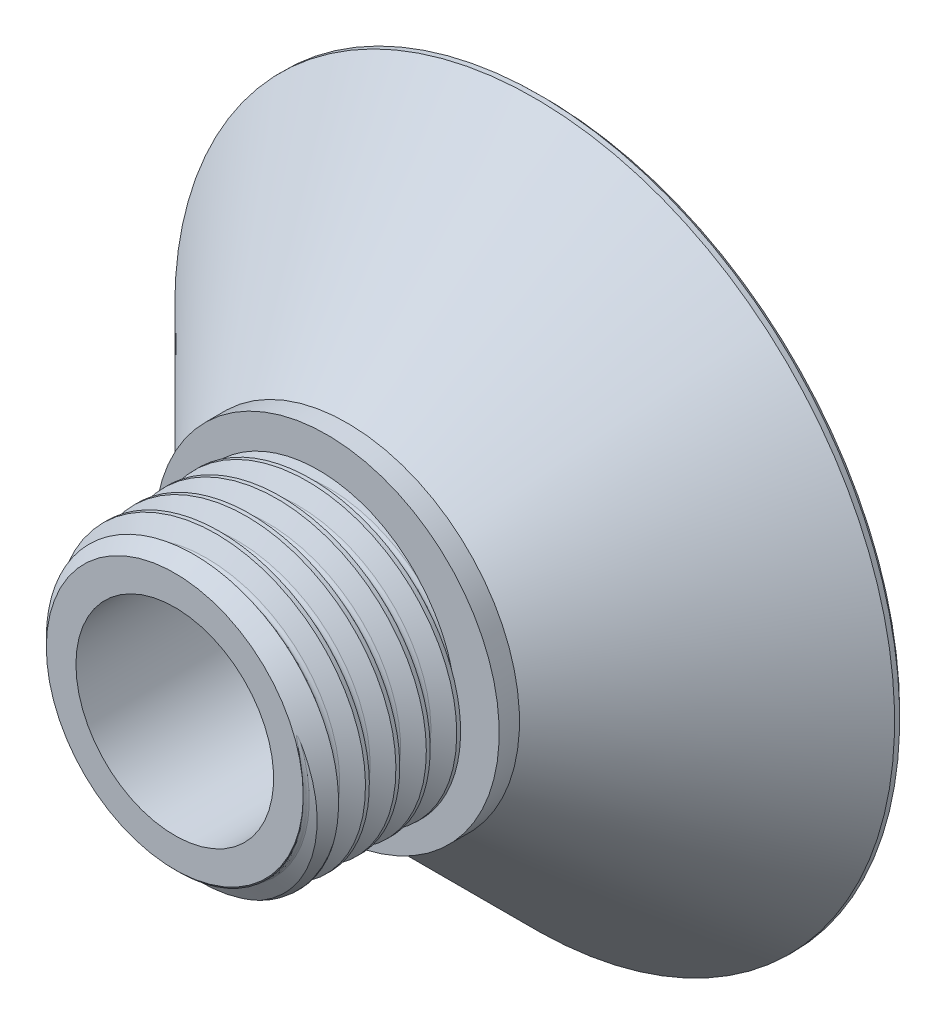
SolidWorks part; units mm, degrees
ref_plane "Front Plane" through (0, 0, 0) normal (0, 0, 1) x (1, 0, 0)
ref_plane "Top Plane" through (0, 0, 0) normal (0, 1, 0) x (1, 0, 0)
ref_plane "Right Plane" through (0, 0, 0) normal (1, 0, 0) x (0, 0, -1)
sketch "Sketch1" plane through (0, 0, 0) normal (1, 0, 0) x (0, 0, -1)
  line L1 (0, 0) -> (-153.1218, 0) construction
  line L2 (0, 6.5) -> (0, 35.5)
  line L3 (0, 35.5) -> (-1, 35.5)
  line L4 (-1, 35.5) -> (-19.5, 17)
  line L5 (-19.5, 17) -> (-21.5, 17)
  line L6 (-21.5, 17) -> (-21.5, 12.67)
  line L7 (-21.5, 12.67) -> (-36.5, 12.67)
  line L8 (-36.5, 12.67) -> (-36.5, 9.75)
  line L9 (-36.5, 9.75) -> (-2, 9.75)
  line L10 (-2, 9.75) -> (-2, 6.5)
  line L11 (-2, 6.5) -> (0, 6.5)
  dimension "D1" = 45
  dimension "D3" = 34
  dimension "D4" = 1
  dimension "D5" = 25.34
  dimension "D6" = 2
  dimension "D7" = 15
  dimension "D8" = 19.5
  dimension "D9" = 13
  dimension "D10" = 2
  dimension "D11" = 21.5
revolve "Revolve1" add sketch "Sketch1" angle 360 about L1
sketch "Sketch2" plane through (0, 0, 21.5) normal (0, 0, 1) x (1, 0, 0)
  circle A0 centre (0, 0) radius 12.67 construction
  circle A1 centre (0, 0) radius 12.67
curve "Helix/Spiral1" pitch 3 height 18 radius 12.67 centre (0, 0, 21.5) axis (0, 0, 1) start towards (1, 0, 0)
sketch "Sketch4" plane through (0, 0, 0) normal (0, 1, 0) x (1, 0, 0)
  line L0 (12.886, -36.1259) -> (14.5, -35.194)
  line L1 (14.5, -35.194) -> (14.5, -34.816)
  line L2 (12.67, -36.5) -> (12.67, -33.51)
  line L3 (-12.67, -36.5) -> (12.67, -36.5) construction
  line L4 (14.5, -35.005) -> (12.67, -35.005) construction
  line L5 (12.886, -33.8841) -> (14.5, -34.816)
  arc A0 (12.886, -36.1259) -> (12.67, -36.5) centre (13.102, -36.5) ccw
  arc A1 (12.886, -33.8841) -> (12.67, -33.51) centre (13.102, -33.51) cw
  spline S0 degree 3 poles (12.67, -21.5) (12.67, -21.5621) (12.0103, -21.6877) (9.1923, -21.875) (4.9748, -22.0625) (0, -22.25) (-4.9748, -22.4375) (-9.1923, -22.625) (-12.0103, -22.8125) (-12.9999, -23) (-12.0103, -23.1875) (-9.1923, -23.375) (-4.9748, -23.5625) (0, -23.75) (4.9748, -23.9375) (9.1923, -24.125) (12.0103, -24.3125) (12.9999, -24.5) (12.0103, -24.6875) (9.1923, -24.875) (4.9748, -25.0625) (0, -25.25) (-4.9748, -25.4375) (-9.1923, -25.625) (-12.0103, -25.8125) (-12.9999, -26) (-12.0103, -26.1875) (-9.1923, -26.375) (-4.9748, -26.5625) (0, -26.75) (4.9748, -26.9375) (9.1923, -27.125) (12.0103, -27.3125) (12.9999, -27.5) (12.0103, -27.6875) (9.1923, -27.875) (4.9748, -28.0625) (0, -28.25) (-4.9748, -28.4375) (-9.1923, -28.625) (-12.0103, -28.8125) (-12.9999, -29) (-12.0103, -29.1875) (-9.1923, -29.375) (-4.9748, -29.5625) (0, -29.75) (4.9748, -29.9375) (9.1923, -30.125) (12.0103, -30.3125) (12.9999, -30.5) (12.0103, -30.6875) (9.1923, -30.875) (4.9748, -31.0625) (0, -31.25) (-4.9748, -31.4375) (-9.1923, -31.625) (-12.0103, -31.8125) (-12.9999, -32) (-12.0103, -32.1875) (-9.1923, -32.375) (-4.9748, -32.5625) (0, -32.75) (4.9748, -32.9375) (9.1923, -33.125) (12.0103, -33.3125) (12.9999, -33.5) (12.0103, -33.6875) (9.1923, -33.875) (4.9748, -34.0625) (0, -34.25) (-4.9748, -34.4375) (-9.1923, -34.625) (-12.0103, -34.8125) (-12.9999, -35) (-12.0103, -35.1875) (-9.1923, -35.375) (-4.9748, -35.5625) (0, -35.75) (4.9748, -35.9375) (9.1923, -36.125) (12.0103, -36.3125) (12.9999, -36.5) (12.0103, -36.6875) (9.1923, -36.875) (4.9748, -37.0625) (0, -37.25) (-4.9748, -37.4375) (-9.1923, -37.625) (-12.0103, -37.8125) (-12.9999, -38) (-12.0103, -38.1875) (-9.1923, -38.375) (-4.9748, -38.5625) (0, -38.75) (4.9748, -38.9375) (9.1923, -39.125) (12.0103, -39.3123) (12.67, -39.4379) (12.67, -39.5) knots 0 0 0 0 0.010417 0.020833 0.03125 0.041667 0.052083 0.0625 0.072917 0.083333 0.09375 0.104167 0.114583 0.125 0.135417 0.145833 0.15625 0.166667 0.177083 0.1875 0.197917 0.208333 0.21875 0.229167 0.239583 0.25 0.260417 0.270833 0.28125 0.291667 0.302083 0.3125 0.322917 0.333333 0.34375 0.354167 0.364583 0.375 0.385417 0.395833 0.40625 0.416667 0.427083 0.4375 0.447917 0.458333 0.46875 0.479167 0.489583 0.5 0.510417 0.520833 0.53125 0.541667 0.552083 0.5625 0.572917 0.583333 0.59375 0.604167 0.614583 0.625 0.635417 0.645833 0.65625 0.666667 0.677083 0.6875 0.697917 0.708333 0.71875 0.729167 0.739583 0.75 0.760417 0.770833 0.78125 0.791667 0.802083 0.8125 0.822917 0.833333 0.84375 0.854167 0.864583 0.875 0.885417 0.895833 0.90625 0.916667 0.927083 0.9375 0.947917 0.958333 0.96875 0.979167 0.989583 1 1 1 1 construction
  dimension "D2" = 0.432
  dimension "D1" = 1.83
  dimension "D3" = 60
  dimension "D4" = 2.99
sweep "Sweep5" add profiles "Sketch4" path "Helix/Spiral1"
sketch "Sketch11" plane through (0, 0, 0) normal (0, 1, 0) x (1, 0, 0)
  line L0 (0, 0) -> (0, -46.1811) construction
  line L1 (17.2033, -36.5) -> (-17.0232, -36.5)
  line L2 (-17, -21.5) -> (17, -21.5) construction
  dimension "D1" = 15
extrude "Cut-Extrude1" cut sketch "Sketch11" against normal through all and the other way through all
sketch "Sketch12" plane through (0, 0, 0) normal (0, 1, 0) x (1, 0, 0)
  line L0 (0, 0) -> (0, -42.7931) construction
  line L1 (12.67, -36.5) -> (15.17, -34)
  line L2 (15.17, -34) -> (15.17, -36.5)
  line L3 (15.17, -36.5) -> (12.67, -36.5)
  dimension "D1" = 45
  dimension "D2" = 2.5
revolve "Cut-Revolve1" cut sketch "Sketch12" angle 360 about L0
chamfer "Chamfer1" distance 0.5 angle 45 2 edges at (-6.5, 0, 0) (-35.5, 0, 0)
